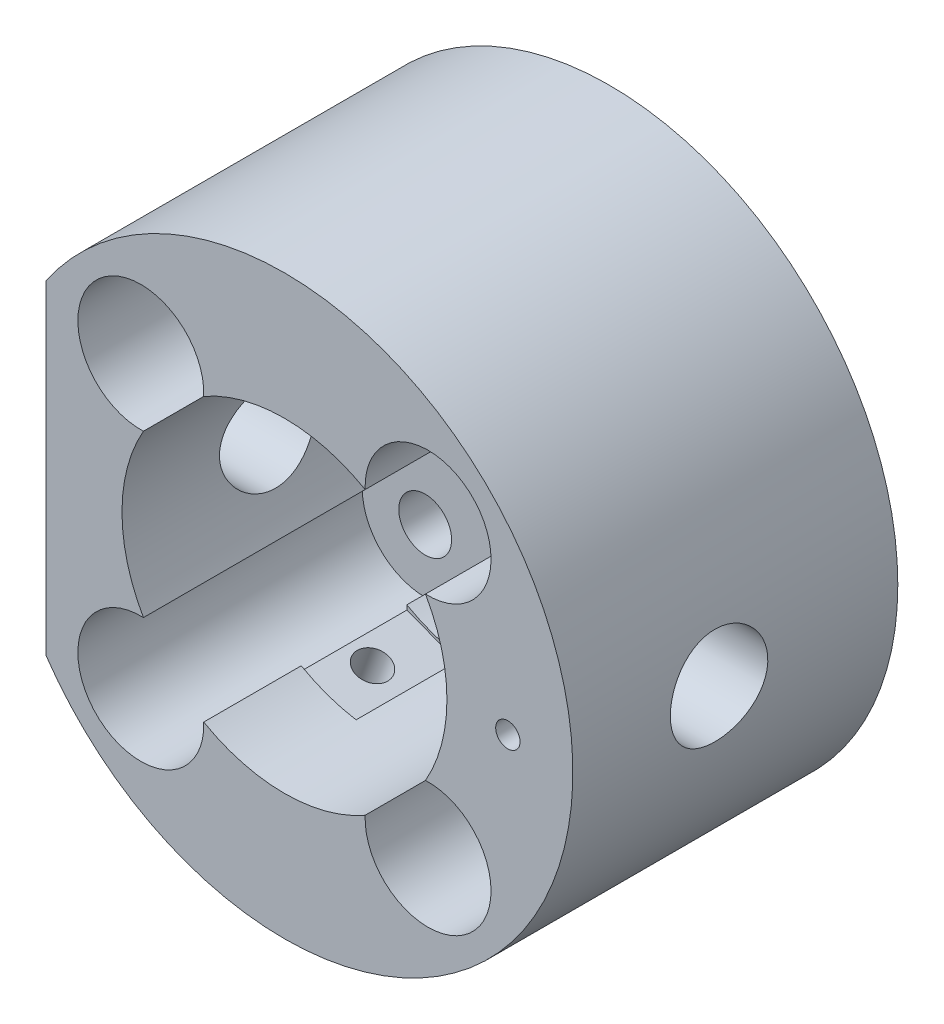
SolidWorks part; units mm, degrees
ref_plane "Alzado" through (0, 0, 0) normal (0, 0, 1) x (1, 0, 0)
ref_plane "Planta" through (0, 0, 0) normal (0, 1, 0) x (1, 0, 0)
ref_plane "Vista lateral" through (0, 0, 0) normal (1, 0, 0) x (0, 0, -1)
sketch "Croquis1" plane through (0, 0, 0) normal (0, 0, 1) x (1, 0, 0)
  line L0 (0, 0) -> (61.4595, 0) construction
  line L1 (0, 0) -> (35.3553, 35.3553) construction
  circle A0 centre (0, 0) radius 25 construction
  circle A1 centre (17.6777, 17.6777) radius 3.25
  circle A2 centre (17.6777, -17.6777) radius 3.25
  circle A3 centre (-17.6777, -17.6777) radius 3.25
  circle A4 centre (-17.6777, 17.6777) radius 3.25
  circle A5 centre (0, 0) radius 35.5
  circle A6 centre (0, 0) radius 3.25
  point P16 (0, 0)
  dimension "D1" = 50
  dimension "D3" = 6.5
  dimension "D6" = 71
  dimension "D7" = 6.5
  dimension "D2" = 45
  dimension "D5" = 39.2699
  dimension "D4" = 4
extrude "Saliente-Extruir1" add sketch "Croquis1" along normal blind 5
sketch "Croquis2" plane through (0, 0, 5) normal (0, 0, 1) x (1, 0, 0)
  line L0 (-29.33, 20) -> (-29.33, -20)
  line L1 (-25.4277, 17.6777) -> (-25.4277, -17.6777)
  arc A0 (-29.33, -20) -> (-29.33, 20) centre (0, 0) ccw
  circle A1 centre (17.6777, -17.6777) radius 3.25 construction
  circle A2 centre (17.6777, 17.6777) radius 3.25 construction
  circle A3 centre (-17.6777, 17.6777) radius 3.25 construction
  circle A4 centre (-17.6777, -17.6777) radius 3.25 construction
  circle A5 centre (17.6777, -17.6777) radius 3.25
  circle A6 centre (17.6777, 17.6777) radius 3.25
  circle A7 centre (-17.6777, 17.6777) radius 3.25
  circle A8 centre (-17.6777, -17.6777) radius 3.25
  circle A9 centre (-17.6777, 17.6777) radius 7.75
  circle A10 centre (17.6777, 17.6777) radius 7.75
  circle A11 centre (17.6777, -17.6777) radius 7.75
  circle A12 centre (-17.6777, -17.6777) radius 7.75
  arc A13 (-29.33, -14.5709) -> (-29.33, 14.5709) centre (0, 0) ccw
  circle A14 centre (0, 0) radius 20
  circle M3 centre (0, 0) radius 35.5
  dimension "D1" = 71
  dimension "D4" = 40
  dimension "D2" = 40
  dimension "D3" = 4.5
extrude "Saliente-Extruir2" add sketch "Croquis2" along normal blind 35 contours A13 L0 M3 | A9 A13 L0 A12 L1 | A14 A10 A13 A9 | A14 A9 L1 A12 | A14 A12 A13 A11 | A14 A11 A13 A10 region at (10.1816, 33.0037, 5) region at (-27.2333, 0, 5) region at (0, 25.894, 5) region at (0, -25.894, 5) region at (-22.488, 0, 5) region at (25.894, 0, 5)
sketch "Croquis3" plane through (-29.33, 0, 0) normal (-1, 0, 0) x (0, 0, 1)
  circle A0 centre (22, 0) radius 6
  dimension "D1" = 12
  dimension "D2" = 22
extrude "Cortar-Extruir1" cut sketch "Croquis3" against normal through all
sketch "Croquis4" plane through (0, 0, 40) normal (0, 0, 1) x (1, 0, 0)
  circle A0 centre (27.5, 0) radius 1.5
  circle A1 centre (0, 0) radius 27.5 construction
  dimension "D1" = 55
  dimension "D2" = 3
extrude "Cortar-Extruir2" cut sketch "Croquis4" against normal up to next
sketch "Croquis5" plane through (0, 0, 5) normal (0, 0, 1) x (1, 0, 0)
  line L0 (-16.2021, -31.5871) -> (-8.7178, -34.4129)
  line L1 (-12.4599, -33) -> (0, 0) construction
  line L2 (-10.9036, -17.554) -> (-3.4193, -20.3799) construction
  arc A0 (-29.33, -20) -> (-29.33, 20) centre (0, 0) ccw construction
  point P10 (-7.1614, -18.967)
  dimension "D1" = 8
  dimension "D2" = 33
  dimension "D3" = 8
  dimension "D4" = 15
extrude "Cortar-Extruir-Lámina1" cut sketch "Croquis5" along normal offset from surface (13 mm away) 11 from offset 11 thin up to face at (29, 0, 40) thin type one direction wall 2
sketch "Croquis6" plane through (-12.4599, -33, 0) normal (-0.3532, -0.9355, 0) x (0.9355, -0.3532, 0)
  line L0 (-4, 29) -> (4, 29) construction
  line L2 (-4, 29) -> (-4, 16) construction
  circle A0 centre (0, 22) radius 2
  dimension "D1" = 4
  dimension "D2" = 7
  dimension "D3" = 4
extrude "Cortar-Extruir3" cut sketch "Croquis6" against normal up to next
sketch "Croquis7" plane through (0, 0, 5) normal (0, 0, 1) x (1, 0, 0)
  line L0 (-10.9036, -17.554) -> (-3.4193, -20.3799)
extrude "Cortar-Extruir-Lámina2" cut sketch "Croquis7" along normal blind 13 from offset 10 thin thin type one direction reverse wall 2
